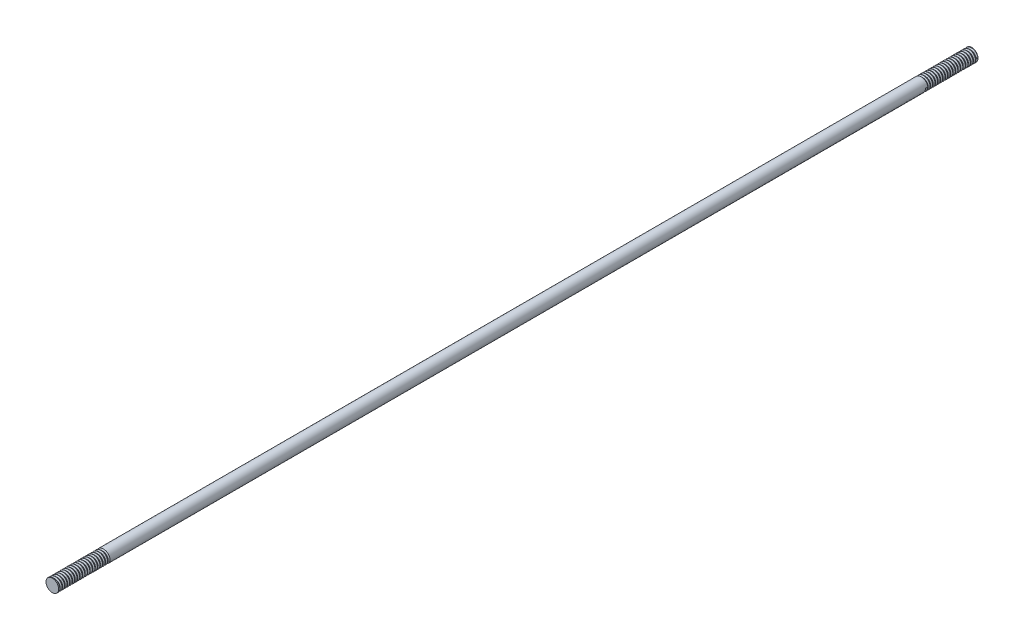
SolidWorks part; units mm, degrees
ref_plane "Front Plane" through (0, 0, 0) normal (0, 0, 1) x (1, 0, 0)
ref_plane "Top Plane" through (0, 0, 0) normal (0, 1, 0) x (1, 0, 0)
ref_plane "Right Plane" through (0, 0, 0) normal (1, 0, 0) x (0, 0, -1)
sketch "Sketch1" plane through (0, 0, 0) normal (0, 0, 1) x (1, 0, 0)
  circle A0 centre (0, 0) radius 3.175
  dimension "D1" = 6.35
extrude "Boss-Extrude1" add sketch "Sketch1" along normal blind 462.435
thread "Thread2" pitch 1.27 method cut profile "Thread Profile1" start angle 2, offset 0, length 25.4, pitch 1.27, diameter 6.35
ref_plane "Plane1" through (3.1731, 0.1108, 0) normal (0.0349, -0.9994, 0) x (0.9994, 0.0349, 0)
sketch "Thread Profile1" plane through (3.1731, 0.1108, 0) normal (0.0349, -0.9994, 0) x (0.9994, 0.0349, 0)
  line L0 (0, 0) -> (0, 1.27) construction
  line L11 (0, 0) -> (0, 1.1112)
  line L12 (0, 1.1112) -> (-0.6874, 0.7144)
  line L13 (-0.6874, 0.7144) -> (-0.6874, 0.3969)
  line L15 (-0.6874, 0.3969) -> (0, 0)
  line L17 (-0.6874, 0.5556) -> (0, 0.5556) construction
  point P2 (0, 0)
  dimension "Pitch" = 1.27
  dimension "Profile_Angle" = 60
  dimension "Profile_Land" = 0.3175
  dimension "Profile_Height" = 0.6874
thread "Thread3" pitch 1.27 method cut profile "Thread Profile2" start angle 2, offset 0, length 25.4, pitch 1.27, diameter 6.35
ref_plane "Plane2" through (-3.1731, 0.1108, 462.435) normal (-0.0349, -0.9994, 0) x (-0.9994, 0.0349, 0)
sketch "Thread Profile2" plane through (-3.1731, 0.1108, 462.435) normal (-0.0349, -0.9994, 0) x (-0.9994, 0.0349, 0)
  line L0 (0, 0) -> (0, 1.27) construction
  line L11 (0, 0) -> (0, 1.1112)
  line L12 (0, 1.1112) -> (-0.6874, 0.7144)
  line L13 (-0.6874, 0.7144) -> (-0.6874, 0.3969)
  line L15 (-0.6874, 0.3969) -> (0, 0)
  line L17 (-0.6874, 0.5556) -> (0, 0.5556) construction
  point P2 (0, 0)
  dimension "Pitch" = 1.27
  dimension "Profile_Angle" = 60
  dimension "Profile_Land" = 0.3175
  dimension "Profile_Height" = 0.6874
ref_axis "Axis1" through (0, 0, 462.435) along (0, 0, -1)
